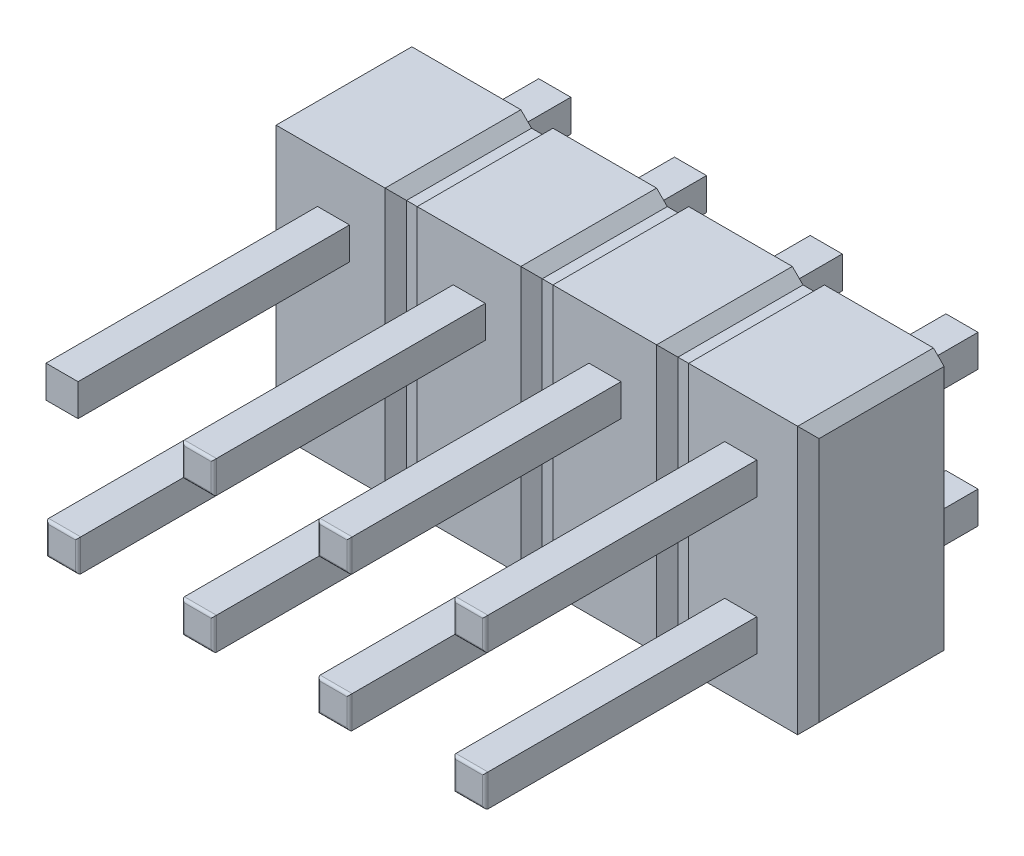
SolidWorks part; units mm, degrees
ref_plane "前视基准面" through (0, 0, 0) normal (0, 0, 1) x (1, 0, 0)
ref_plane "上视基准面" through (0, 0, 0) normal (0, 1, 0) x (1, 0, 0)
ref_plane "右视基准面" through (0, 0, 0) normal (1, 0, 0) x (0, 0, -1)
sketch "草图1" plane through (0, 0, 0) normal (0, 0, 1) x (1, 0, 0)
  line L0 (0, -1000) -> (0, 49000) construction
  line L1 (-1000, 0) -> (49000, 0) construction
  line L2 (5.08, 2.5) -> (-5.08, 2.5)
  line L3 (-5.08, 2.5) -> (-5.08, 0)
  line L4 (-5.08, -2.5) -> (-5.08, 0)
  line L5 (5.08, -2.5) -> (-5.08, -2.5)
  line L6 (5.08, -2.5) -> (5.08, 0)
  line L7 (5.08, 2.5) -> (5.08, 0)
  point P11 (0, -2.5)
  point P13 (0, 2.5)
  dimension "D1" = 5
  dimension "D2" = 10.16
extrude "凸台-拉伸1" add sketch "草图1" along normal blind 2.54
sketch "草图2" plane through (0, 0, 2.54) normal (0, 0, 1) x (1, 0, 0)
  line L0 (-5.08, 0) -> (5.08, 0) construction
  line L1 (-5.08, 2.5) -> (-5.08, -2.5) construction
  line L2 (5.08, -2.5) -> (5.08, 2.5) construction
  line L3 (0, 2.5) -> (0, -2.5) construction
  line L4 (5.08, 2.5) -> (-5.08, 2.5) construction
  line L5 (-5.08, -2.5) -> (5.08, -2.5) construction
  line L6 (-3.8189, 1.5699) -> (-3.8057, 0.9701) construction
  line L7 (-4.1056, 1.27) -> (-3.5058, 1.27) construction
  line L30 (-4.1056, 1.5699) -> (-4.1056, 0.9701)
  line L31 (-4.1056, 1.5699) -> (-3.5058, 1.5699)
  line L32 (-3.5058, 1.5699) -> (-3.5058, 0.9701)
  line L33 (-4.1056, 0.9701) -> (-3.5058, 0.9701)
  circle A0 centre (-3.8123, 1.27) radius 0.3 construction
  dimension "D1" = 0.6
  dimension "D4" = 2
  dimension "D6" = 2
extrude "凸台-拉伸2" add sketch "草图2" along normal mid plane 10.16
sketch "草图4" plane through (0, 0, 2.54) normal (0, 0, 1) x (1, 0, 0)
  line L0 (-2.54, 2.5) -> (-2.54, -2.5) construction
  line L1 (5.08, 2.5) -> (-5.08, 2.5) construction
  line L2 (-5.08, -2.5) -> (5.08, -2.5) construction
  line L3 (-5.08, 2.5) -> (-5.08, -2.5) construction
  line L4 (-2.64, 2.5) -> (-2.64, -2.5)
  line L5 (-2.44, 2.5) -> (-2.44, -2.5)
  line L6 (-2.64, 2.5) -> (-2.44, 2.5)
  line L7 (-2.64, -2.5) -> (-2.44, -2.5)
  dimension "D1" = 2.54
  dimension "D2" = 0.2
extrude "切除-拉伸2" cut sketch "草图4" against normal blind 0.2
sketch "草图5" plane through (0, 0, 2.54) normal (0, 0, 1) x (1, 0, 0)
  line L0 (-2.64, 2.5) -> (-2.44, 2.5)
  line L1 (-2.44, 2.5) -> (-2.44, 2.3)
  line L2 (-2.44, -2.5) -> (-2.44, 2.5) construction
  line L3 (-2.44, 2.3) -> (-2.64, 2.3)
  line L4 (-2.64, 2.5) -> (-2.64, -2.5) construction
  line L5 (-2.64, 2.3) -> (-2.64, 2.5)
  line L6 (-5.08, 0) -> (5.08, 0) construction
  line L7 (-5.08, 2.5) -> (-5.08, -2.5) construction
  line L8 (5.08, -2.5) -> (5.08, 2.5) construction
  line L9 (-2.64, -2.3) -> (-2.64, -2.5)
  line L10 (-2.44, -2.3) -> (-2.64, -2.3)
  line L11 (-2.44, -2.5) -> (-2.44, -2.3)
  line L12 (-2.64, -2.5) -> (-2.44, -2.5)
  dimension "D1" = 0.2
extrude "切除-拉伸3" cut sketch "草图5" against normal up to next
pattern_linear "阵列(线性)2" count 3 spacing 2.54 along (1, 0, 0) of "切除-拉伸3", "切除-拉伸2"
chamfer "倒角1" distance 0.2 angle 45 6 edges at (5.08, 2.5, 1.27) (5.08, 0, 2.54) (5.08, -2.5, 1.27) (-5.08, 2.5, 1.27) (-5.08, -2.5, 1.27) (-5.08, 0, 2.54)
chamfer "倒角2" distance 0.2 angle 45 18 edges at (-2.64, -2.5, 1.27) (2.44, -2.5, 1.27) (0.1, -2.5, 1.27) (2.64, -2.5, 1.27) (-0.1, -2.5, 1.27) (-2.44, -2.5, 1.27) (2.64, 0, 2.54) (-2.64, 0, 2.54) (-0.1, 0, 2.54) (-2.44, 0, 2.54) (2.44, 0, 2.54) (0.1, 0, 2.54) (2.64, 2.5, 1.27) (-0.1, 2.5, 1.27) (-2.44, 2.5, 1.27) (2.44, 2.5, 1.27) (0.1, 2.5, 1.27) (-2.64, 2.5, 1.27)
pattern_linear "阵列(线性)3" count 4 spacing 2.54 along (1, 0, 0) count 2 spacing 2.54 along (0, -1, 0) of "凸台-拉伸2"
fillet "圆角4" radius 0.05 56 edges at (4.1142, -1.27, 7.62) (3.8143, -1.5699, 7.62) (3.5144, -1.27, 7.62) (3.8143, -0.9701, 7.62) (1.5742, -1.27, 7.62) (1.2743, -1.5699, 7.62) (0.9744, -1.27, 7.62) (1.2743, -0.9701, 7.62) (1.5742, 1.27, 7.62) (1.2743, 0.9701, 7.62) (0.9744, 1.27, 7.62) (1.2743, 1.5699, 7.62) (-0.9658, 1.27, 7.62) (-1.2657, 0.9701, 7.62) (-1.5656, 1.27, 7.62) (-1.2657, 1.5699, 7.62) (-0.9658, -1.27, 7.62) (-1.2657, -1.5699, 7.62) (-1.5656, -1.27, 7.62) (-1.2657, -0.9701, 7.62) (-3.5058, -1.27, 7.62) (-3.8057, -1.5699, 7.62) (-4.1056, -1.27, 7.62) (-3.8057, -0.9701, 7.62) (3.5144, 1.27, -2.54) (3.8143, 0.9701, -2.54) (4.1142, 1.27, -2.54) (3.8143, 1.5699, -2.54) (3.5144, -1.27, -2.54) (3.8143, -1.5699, -2.54) (4.1142, -1.27, -2.54) (3.8143, -0.9701, -2.54) (0.9744, -1.27, -2.54) (1.2743, -1.5699, -2.54) (1.5742, -1.27, -2.54) (1.2743, -0.9701, -2.54) (0.9744, 1.27, -2.54) (1.2743, 0.9701, -2.54) (1.5742, 1.27, -2.54) (1.2743, 1.5699, -2.54) (-1.5656, 1.27, -2.54) (-1.2657, 0.9701, -2.54) (-0.9658, 1.27, -2.54) (-1.2657, 1.5699, -2.54) (3.5144, 1.27, 7.62) (4.1142, 1.27, 7.62) (3.8143, 0.9701, 7.62) (3.8143, 1.5699, 7.62) (-1.2657, -1.5699, -2.54) (-0.9658, -1.27, -2.54) (-1.5656, -1.27, -2.54) (-1.2657, -0.9701, -2.54) (-3.8057, -1.5699, -2.54) (-4.1056, -1.27, -2.54) (-3.5058, -1.27, -2.54) (-3.8057, -0.9701, -2.54)
sketch "草图6" plane through (0, -2.5, 0) normal (0, -1, 0) x (1, 0, 0)
  line L0 (-4.88, 0) -> (-2.84, 0) construction
  line L1 (-6.0047, -1.6) -> (7.314, -1.6)
  line L2 (-6.0047, -1.6) -> (-6.0047, -6.4769)
  line L3 (-6.0047, -6.4769) -> (7.314, -6.4769)
  line L4 (7.314, -1.6) -> (7.314, -6.4769)
  dimension "D1" = 1.6
extrude "切除-拉伸4" cut sketch "草图6" against normal blind 10
